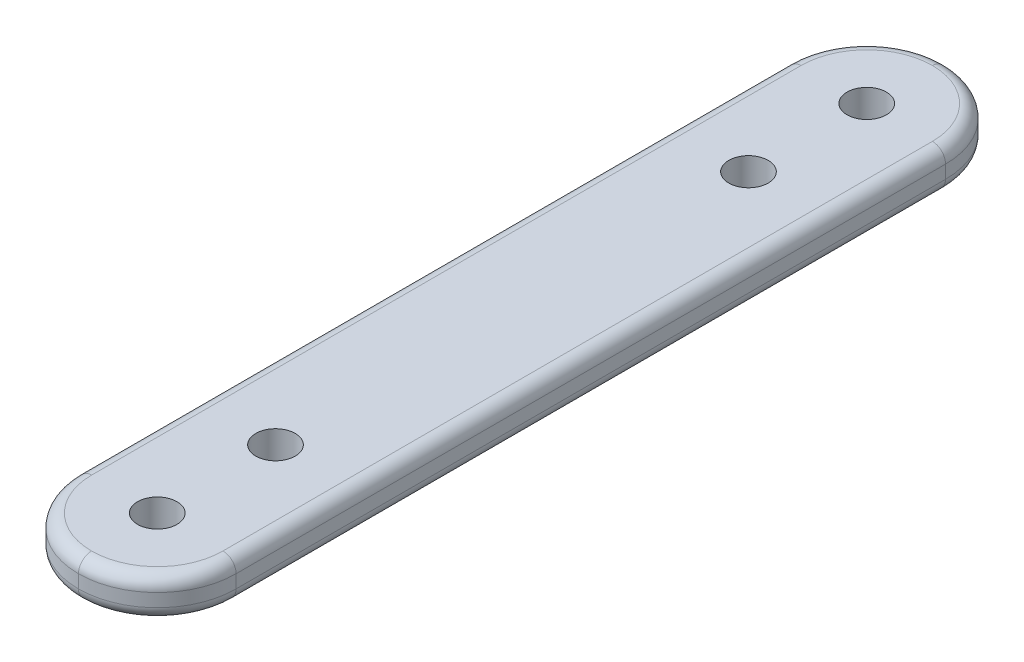
SolidWorks part; units mm, degrees
material "6061 Alloy"
ref_plane "Front Plane" through (0, 0, 0) normal (0, 0, 1) x (1, 0, 0)
ref_plane "Top Plane" through (0, 0, 0) normal (0, 1, 0) x (1, 0, 0)
ref_plane "Right Plane" through (0, 0, 0) normal (1, 0, 0) x (0, 0, -1)
sketch "Sketch1" plane through (0, 0, 0) normal (0, 1, 0) x (1, 0, 0)
  line L0 (0, 69.85) -> (0, -69.85) construction
  line L1 (-12.7, -69.85) -> (12.7, -69.85)
  line L2 (-12.7, -69.85) -> (-12.7, 69.85)
  line L3 (-12.7, 69.85) -> (12.7, 69.85)
  line L4 (12.7, -69.85) -> (12.7, 69.85)
  line L5 (-12.7, -69.85) -> (12.7, 69.85) construction
  line L6 (-12.7, 69.85) -> (12.7, -69.85) construction
  circle A0 centre (0, -57.15) radius 3.175
  circle A1 centre (0, 38.1) radius 3.175
  circle A2 centre (0, 57.15) radius 3.175
  circle A3 centre (0, -38.1) radius 3.175
  point P0 (0, 0)
  dimension "D3" = 6.35
  dimension "D1" = 6.35
  dimension "D8" = 76.2
  dimension "D2" = 25.4
  dimension "D4" = 19.05
  dimension "D5" = 19.05
  dimension "D6" = 12.7
  dimension "D7" = 12.7
extrude "Boss-Extrude1" add sketch "Sketch1" along normal blind 6.35
fillet "Fillet2" radius 12.7 4 edges at (-12.7, 3.175, -69.85) (12.7, 3.175, -69.85) (-12.7, 3.175, 69.85) (12.7, 3.175, 69.85)
fillet "Fillet3" radius 2.1167 12 edges at (8.9803, 6.35, 66.1303) (-8.9803, 6.35, 66.1303) (-12.7, 6.35, 0) (-8.9803, 6.35, -66.1303) (8.9803, 6.35, -66.1303) (8.9803, 0, 66.1303) (-8.9803, 0, 66.1303) (-12.7, 0, 0) (-8.9803, 0, -66.1303) (8.9803, 0, -66.1303) (12.7, 6.35, 0) (12.7, 0, 0)
